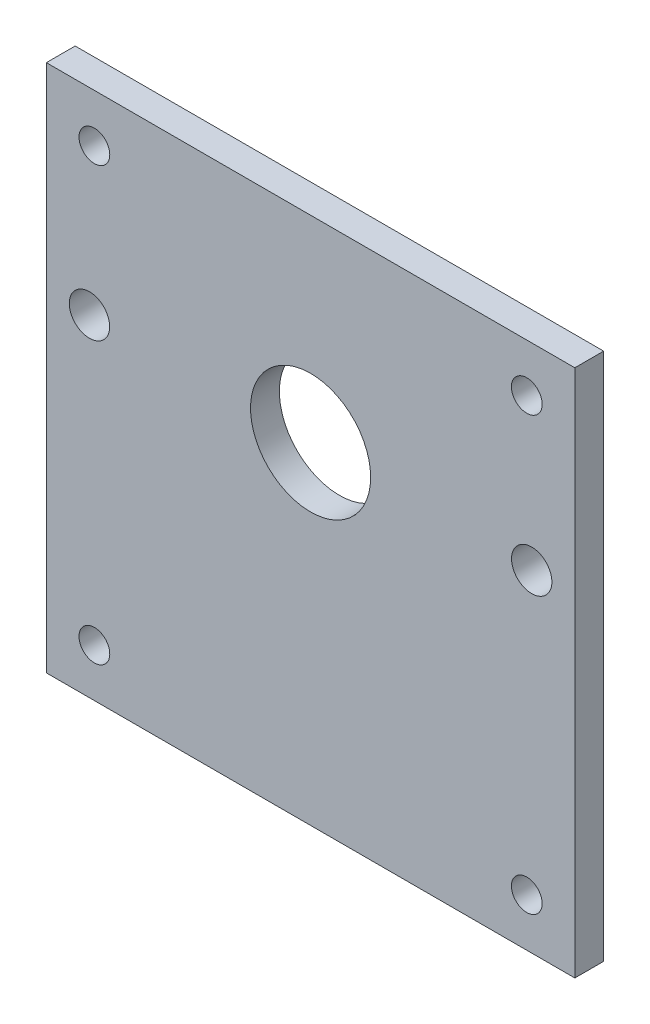
SolidWorks part; units mm, degrees
material "5052-H34"
ref_plane "正面" through (0, 0, 0) normal (0, 0, 1) x (1, 0, 0)
ref_plane "平面" through (0, 0, 0) normal (0, 1, 0) x (1, 0, 0)
ref_plane "右側面" through (0, 0, 0) normal (1, 0, 0) x (0, 0, -1)
sketch "ｽｹｯﾁ1" plane through (0, 0, 0) normal (0, 0, 1) x (1, 0, 0)
  line L0 (0, 0) -> (0, 15.5) construction
  line L1 (-27.5, 22.5) -> (27.5, 22.5) construction
  line L2 (-27.5, 27.5) -> (27.5, 27.5)
  line L3 (-27.5, 27.5) -> (-27.5, -27.5)
  line L4 (-27.5, -27.5) -> (27.5, -27.5)
  line L5 (27.5, 27.5) -> (27.5, -27.5)
  line L6 (-27.5, 27.5) -> (27.5, -27.5) construction
  line L7 (-27.5, -27.5) -> (27.5, 27.5) construction
  line L8 (-27.5, -22.5) -> (27.5, -22.5) construction
  circle A0 centre (0, 0) radius 15.5 construction
  circle A1 centre (0, 7) radius 6.25
  circle A5 centre (-22.5, 22.5) radius 1.6
  circle A6 centre (22.5, 22.5) radius 1.6
  circle A7 centre (-22.5, -22.5) radius 1.6
  circle A8 centre (22.5, -22.5) radius 1.6
  circle A9 centre (-23.0125, 7) radius 2.1
  circle A10 centre (23.0125, 7) radius 2.1
  point P15 (0, 0)
  dimension "D1" = 31
  dimension "D2" = 12.5
  dimension "D10" = 3.2
  dimension "D11" = 3.2
  dimension "D12" = 3.2
  dimension "D13" = 3.2
  dimension "D4" = 4.2
  dimension "D19" = 4.2
  dimension "D3" = 7
  dimension "D6" = 55
  dimension "D7" = 55
  dimension "D8" = 5
  dimension "D9" = 5
  dimension "D14" = 5
  dimension "D15" = 5
  dimension "D16" = 5
  dimension "D17" = 5
  dimension "D5" = 23.0125
  dimension "D18" = 23.0125
extrude "ﾎﾞｽ - 押し出し1" add sketch "ｽｹｯﾁ1" along normal blind 3
equation "\"D18@ｽｹｯﾁ1\"=\"D5@ｽｹｯﾁ1\""
equation "\"D5@ｽｹｯﾁ1\"=46.025/2"
